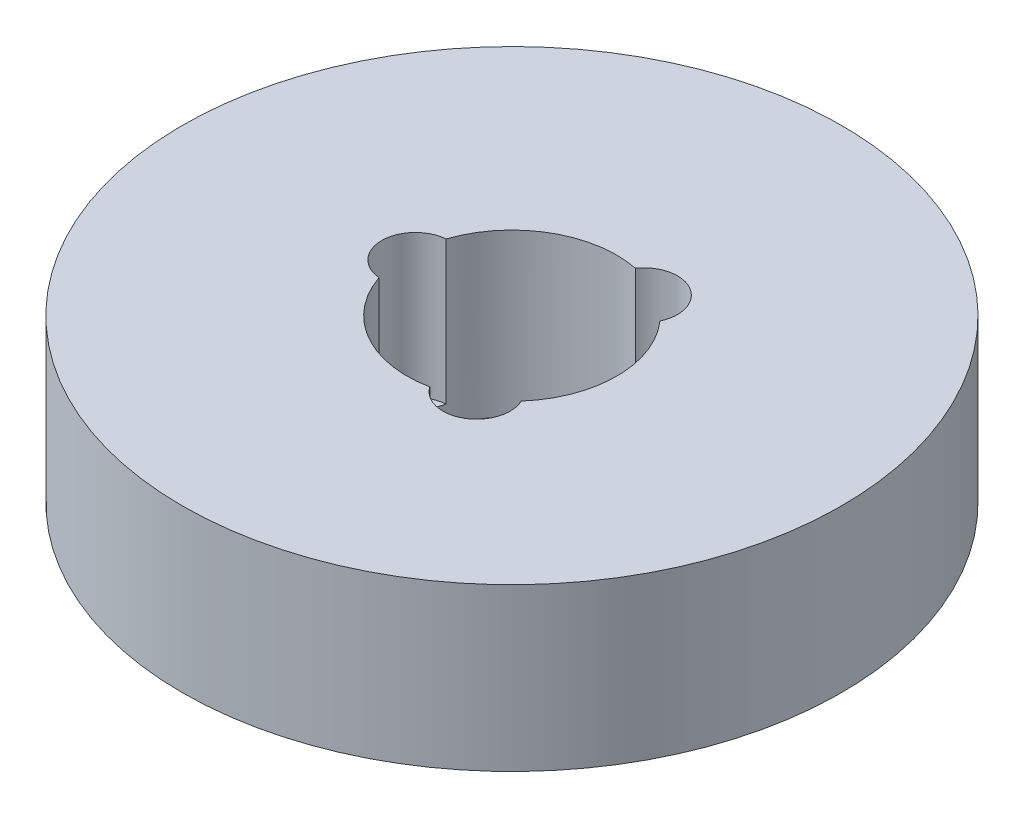
SolidWorks part; units mm, degrees
ref_plane "Front Plane" through (0, 0, 0) normal (0, 0, 1) x (1, 0, 0)
ref_plane "Top Plane" through (0, 0, 0) normal (0, 1, 0) x (1, 0, 0)
ref_plane "Right Plane" through (0, 0, 0) normal (1, 0, 0) x (0, 0, -1)
sketch "Sketch1" plane through (0, 0, 0) normal (0, 1, 0) x (1, 0, 0)
  circle A0 centre (0, 0) radius 55
  dimension "FLANGE_OD" = 110
extrude "Boss-Extrude1" add sketch "Sketch1" along normal blind 27
sketch "Sketch2" plane through (0, 0, 0) normal (0, 1, 0) x (1, 0, 0)
  circle A0 centre (0, 0) radius 17.5
  dimension "BORE_D" = 35
extrude "Cut-Extrude1" cut sketch "Sketch2" along normal through all
sketch "Sketch3" plane through (0, 27, 0) normal (0, 1, 0) x (1, 0, 0)
  circle A0 centre (0, 0) radius 16.1176 construction
  circle A1 centre (-16.1176, 0) radius 5.6091
  dimension "BOLT_D" = 11.2183
  dimension "BOLT_PCD" = 32.2352
extrude "Cut-Extrude2" cut sketch "Sketch3" against normal blind 23.8602
pattern_circular "CirPattern1" count 3 over 360 about axis through (0, 0, 0) along (0, 1, 0) of "Cut-Extrude2"
